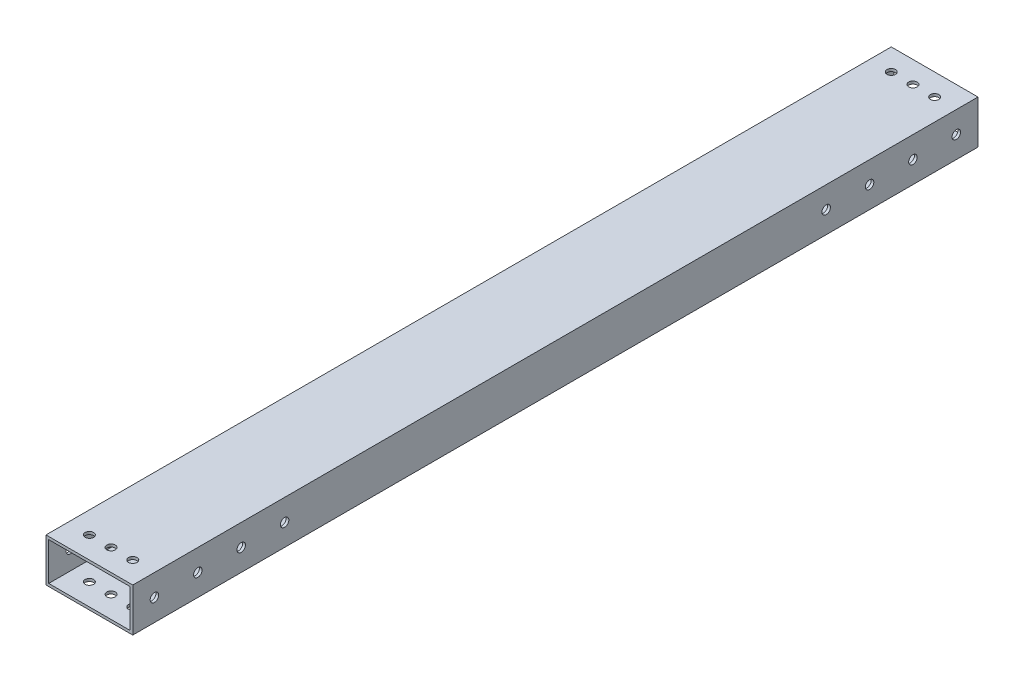
SolidWorks part; units mm, degrees
material "6061-T6 (SS)"
ref_plane "Front Plane" through (0, 0, 0) normal (0, 0, 1) x (1, 0, 0)
ref_plane "Top Plane" through (0, 0, 0) normal (0, 1, 0) x (1, 0, 0)
ref_plane "Right Plane" through (0, 0, 0) normal (1, 0, 0) x (0, 0, -1)
sketch "Sketch1" plane through (0, 0, 0) normal (0, 0, 1) x (1, 0, 0)
  line L0 (-23.8125, 11.1125) -> (23.8125, 11.1125)
  line L1 (-25.4, -12.7) -> (25.4, -12.7)
  line L2 (-25.4, -12.7) -> (-25.4, 12.7)
  line L3 (-25.4, 12.7) -> (25.4, 12.7)
  line L4 (25.4, -12.7) -> (25.4, 12.7)
  line L5 (-25.4, -12.7) -> (25.4, 12.7) construction
  line L6 (-25.4, 12.7) -> (25.4, -12.7) construction
  line L7 (23.8125, -11.1125) -> (23.8125, 11.1125)
  line L8 (-23.8125, -11.1125) -> (23.8125, -11.1125)
  line L9 (-23.8125, -11.1125) -> (-23.8125, 11.1125)
  point P0 (0, 0)
  dimension "D1" = 50.8
  dimension "D2" = 25.4
  dimension "D3" = 1.5875
extrude "Boss-Extrude1" add sketch "Sketch1" along normal mid plane 494.95
sketch "Sketch2" plane through (0, 12.7, 0) normal (0, 1, 0) x (1, 0, 0)
  line L0 (25.4, 247.475) -> (-25.4, 247.475) construction
  line L1 (-25.4, 0) -> (25.4, 0) construction
  line L2 (-25.4, -247.475) -> (-25.4, 247.475) construction
  line L3 (25.4, -247.475) -> (25.4, 247.475) construction
  circle A0 centre (-12.7, 234.775) radius 2.4892
  circle A1 centre (0, 234.775) radius 2.4892
  circle A2 centre (12.7, 234.775) radius 2.4892
  circle A3 centre (12.7, -234.775) radius 2.4892
  circle A4 centre (0, -234.775) radius 2.4892
  circle A5 centre (-12.7, -234.775) radius 2.4892
  point P9 (0, 247.475)
  dimension "D1" = 4.9784
  dimension "D2" = 12.7
  dimension "D3" = 12.7
  dimension "D4" = 12.7
extrude "Cut-Extrude1" cut sketch "Sketch2" against normal through all
sketch "Sketch3" plane through (25.4, 0, 0) normal (1, 0, 0) x (0, 0, -1)
  line L0 (247.475, -12.7) -> (247.475, 12.7) construction
  line L1 (0, 12.7) -> (0, -12.7) construction
  line L2 (-247.475, 12.7) -> (247.475, 12.7) construction
  line L3 (-247.475, -12.7) -> (247.475, -12.7) construction
  circle A0 centre (234.775, 0) radius 2.4892
  circle A1 centre (-234.775, 0) radius 2.4892
  circle A2 centre (209.375, 0) radius 2.4892
  circle A3 centre (183.975, 0) radius 2.4892
  circle A4 centre (158.575, 0) radius 2.4892
  circle A7 centre (-158.575, 0) radius 2.4892
  circle A8 centre (-183.975, 0) radius 2.4892
  circle A9 centre (-209.375, 0) radius 2.4892
  point P5 (247.475, 0)
  dimension "D1" = 12.7
  dimension "D2" = 4.9784
  dimension "D4" = 25.4
  dimension "D3" = 4
extrude "Cut-Extrude2" cut sketch "Sketch3" against normal through all
